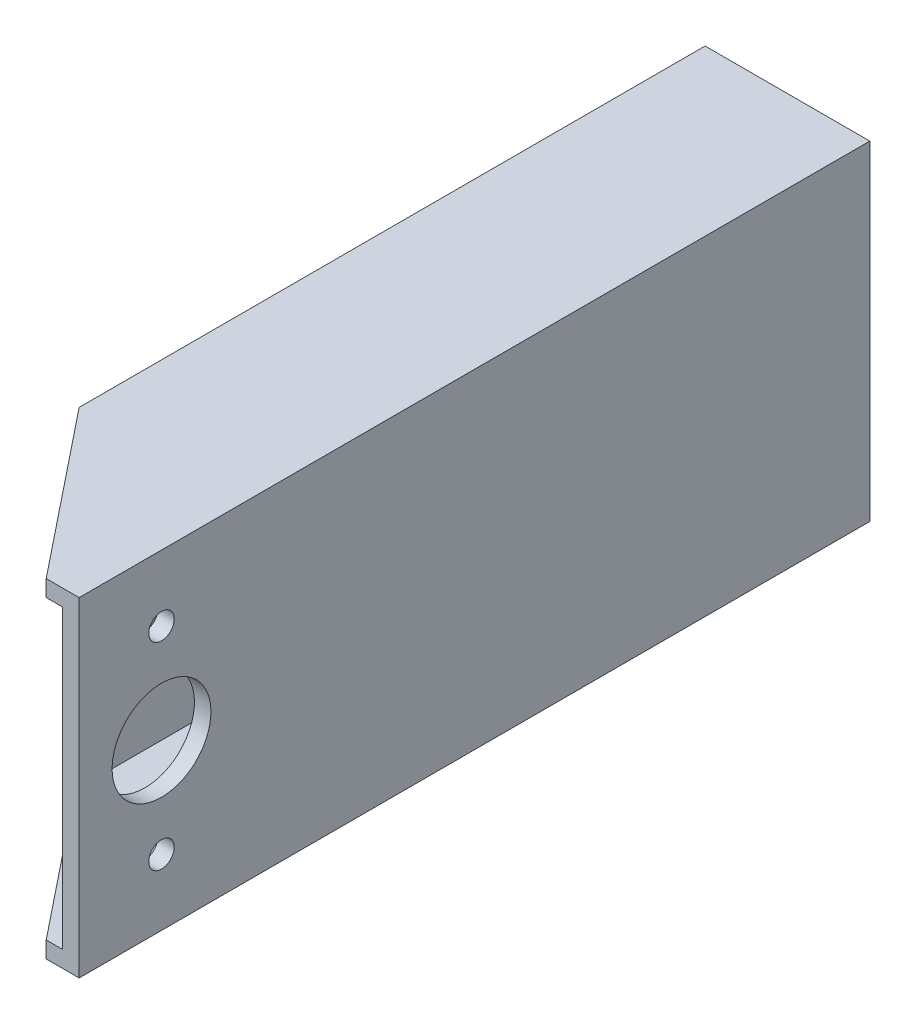
SolidWorks part; units mm, degrees
ref_plane "Front Plane" through (0, 0, 0) normal (0, 0, 1) x (1, 0, 0)
ref_plane "Top Plane" through (0, 0, 0) normal (0, 1, 0) x (1, 0, 0)
ref_plane "Right Plane" through (0, 0, 0) normal (1, 0, 0) x (0, 0, -1)
sketch "Sketch1" plane through (0, 0, 0) normal (0, 0, 1) x (1, 0, 0)
  line L1 (-12.1647, 2.5103) -> (19.5853, 2.5103)
  line L2 (-12.1647, 2.5103) -> (-12.1647, -60.9897)
  line L3 (-12.1647, -60.9897) -> (19.5853, -60.9897)
  line L4 (19.5853, 2.5103) -> (19.5853, -60.9897)
  line L5 (-8.9897, -0.6647) -> (16.4103, -0.6647)
  line L6 (-8.9897, -0.6647) -> (-8.9897, -57.8147)
  line L7 (-8.9897, -57.8147) -> (16.4103, -57.8147)
  line L8 (16.4103, -0.6647) -> (16.4103, -57.8147)
  dimension "D1" = 63.5
  dimension "D2" = 31.75
  dimension "D3" = 3.175
  dimension "D4" = 3.175
  dimension "D5" = 3.175
  dimension "D6" = 3.175
extrude "Boss-Extrude1" add sketch "Sketch1" along normal blind 152.4
sketch "Sketch2" plane through (0, 2.5103, 0) normal (0, 1, 0) x (1, 0, 0)
  line L0 (13.2353, -152.4) -> (-12.1647, -120.65)
  line L1 (19.5853, -152.4) -> (-12.1647, -152.4) construction
  line L2 (-12.1647, -152.4) -> (-12.1647, 0) construction
  line L3 (-12.1647, -120.65) -> (-12.1647, -152.4)
  line L4 (-12.1647, -152.4) -> (13.2353, -152.4)
  line L5 (13.2353, -152.4) -> (13.5724, -152.4399)
  line M4 (-12.1647, 0) -> (-12.1647, -152.4)
  line M5 (-12.1647, -152.4) -> (19.5853, -152.4)
  dimension "D1" = 31.75
  dimension "D2" = 25.4
extrude "Cut-Extrude1" cut sketch "Sketch2" against normal up to surface (63.5 mm away) contours L0 M5 M4 region at (-3.6981, 2.5103, 141.8167) up to face at (3.7103, -60.9897, 76.2)
sketch "Sketch3" plane through (16.4103, 0, 0) normal (-1, 0, 0) x (0, 0, 1)
  line L0 (152.4, -57.8147) -> (152.4, -0.6647) construction
  line L1 (120.65, -60.9897) -> (152.4, -60.9897) construction
  line L2 (152.4, -29.2397) -> (124.6188, -29.2397)
  line L3 (124.6188, -57.8147) -> (124.6188, -0.6647) construction
  circle A0 centre (136.525, -29.2397) radius 9.525
  point P0 (136.525, -48.2897)
  point P9 (136.525, -10.1897)
  dimension "D1" = 15.875
  dimension "D2" = 12.7
extrude "Cut-Extrude2" cut sketch "Sketch3" against normal up to surface (3.175 mm away) contours A0 up to face at (19.5853, -29.2397, 76.2)
hole_wizard "#10 (0.1935) Diameter Hole1" positions "3DSketch1" profile "Sketch4" hole size "#10" standard "ANSI Inch" end condition through all
sketch3d "3DSketch1"
  point P0 (16.4103, -48.2897, 136.525)
  point P3 (16.4103, -10.1897, 136.525)
sketch "Sketch4" plane through (16.4103, -48.2897, 136.525) normal (0, 1, 0) x (0, 0, 1)
  line L0 (0, 0) -> (0, 3.175)
  line L1 (0, 3.175) -> (2.4574, 3.175)
  line L2 (2.4574, 3.175) -> (2.4574, 0)
  line L5 (2.4574, 0) -> (0, 0)
  line L11 (0, -6.35) -> (0, 107.95) construction
  dimension "Thru Hole Dia." = 4.9149
  dimension "Thru Hole Depth" = 3.175
